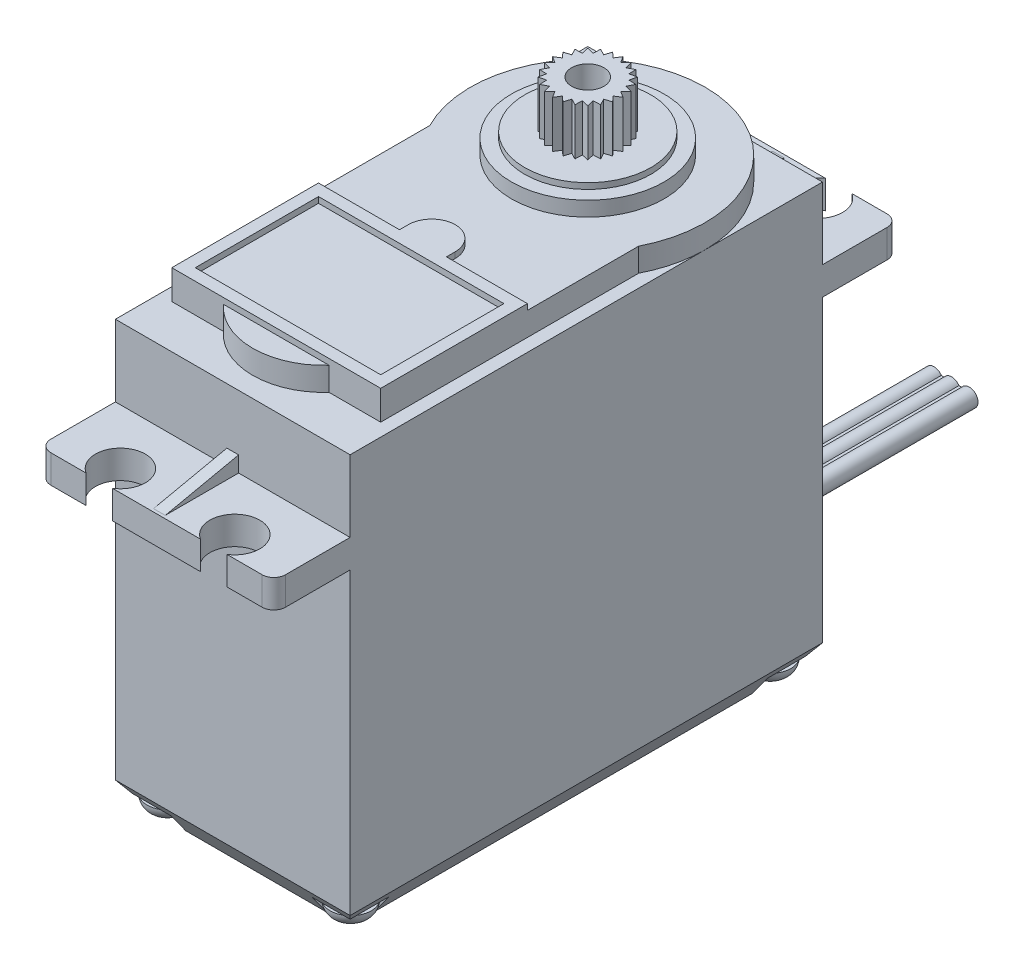
SolidWorks part; units mm, degrees
ref_plane "Front" through (0, 0, 0) normal (0, 0, 1) x (1, 0, 0)
ref_plane "Top" through (0, 0, 0) normal (0, 1, 0) x (1, 0, 0)
ref_plane "Right" through (0, 0, 0) normal (1, 0, 0) x (0, 0, -1)
sketch "Sketch1" plane through (0, 0, 0) normal (0, 1, 0) x (1, 0, 0)
  line L5 (-10, 20.125) -> (10, 20.125)
  line L6 (-10, 20.125) -> (-10, -20.125)
  line L7 (-10, -20.125) -> (10, -20.125)
  line L8 (10, 20.125) -> (10, -20.125)
  line L9 (-10, 20.125) -> (10, -20.125) construction
  line L10 (-10, -20.125) -> (10, 20.125) construction
  point P0 (0, 0)
  dimension "D1" = 20
  dimension "D2" = 40.25
extrude "Boss-Extrude1" add sketch "Sketch1" along normal mid plane 36.75
ref_plane "Plane1" through (0, 9.875, 0) normal (0, 1, 0) x (1, 0, 0)
sketch "Sketch2" plane through (0, 9.875, 0) normal (0, 1, 0) x (1, 0, 0)
  line L0 (-10, -20.125) -> (-10, -26.625)
  line L1 (-10, -26.625) -> (-6, -26.625)
  line L2 (-3.75, -26.625) -> (3.75, -26.625)
  line L3 (6, -26.625) -> (10, -26.625)
  line L4 (10, -26.625) -> (10, -20.125)
  line L5 (0, -26.625) -> (0, -20.125) construction
  line L6 (-10, -20.125) -> (10, -20.125) construction
  line L7 (-10, -20.125) -> (10, -20.125)
  arc A0 (-6, -26.625) -> (-3.75, -26.625) centre (-4.875, -24.8222) cw
  arc A1 (3.75, -26.625) -> (6, -26.625) centre (4.875, -24.8222) cw
  dimension "D1" = 2.125
  dimension "D2" = 7.5
  dimension "D3" = 6.5
  dimension "D4" = 2.25
extrude "Boss-Extrude2" add sketch "Sketch2" along normal blind 2.4
sketch "Sketch3" plane through (0, 0, 0) normal (1, 0, 0) x (0, 0, -1)
  line L0 (-20.125, 13.615) -> (-26.375, 12.275)
  line L1 (-20.125, 18.375) -> (-20.125, 12.275) construction
  line L2 (-26.375, 12.275) -> (-20.125, 12.275)
  line L3 (-20.125, 12.275) -> (-26.625, 12.275) construction
  line L4 (-20.125, 12.275) -> (-20.125, 13.615)
  line L5 (-26.625, 12.275) -> (-26.625, 9.875) construction
  dimension "D1" = 1.34
  dimension "D2" = 0.25
extrude "Boss-Extrude3" add sketch "Sketch3" along normal mid plane 1
sketch "Sketch4" plane through (0, 18.375, 0) normal (0, 1, 0) x (1, 0, 0)
  line L0 (-10, 20.125) -> (-10, -20.125) construction
  line L1 (10, -20.125) -> (10, 20.125) construction
  line L2 (-8.9, 5.5654) -> (-8.9, -16.419)
  line L3 (-8.9, -16.419) -> (-4.5, -16.419)
  line L4 (4.5, -16.419) -> (8.9, -16.419)
  line L5 (8.9, -16.419) -> (8.9, 5.5654)
  line L6 (-4.5, -16.419) -> (4.5, -16.419) construction
  line L7 (0, -16.419) -> (0, -18.419) construction
  line L12 (10, -20.125) -> (10, 20.125)
  line L13 (10, 20.125) -> (-10, 20.125)
  line L14 (-10, 20.125) -> (-10, -20.125)
  line L15 (-10, -20.125) -> (10, -20.125)
  line L16 (10, -20.125) -> (10, 20.125)
  line L17 (10, 20.125) -> (-10, 20.125)
  line L18 (-10, 20.125) -> (-10, -20.125)
  line L19 (-10, -20.125) -> (10, -20.125)
  arc A0 (-8.9, 5.5654) -> (8.9, 5.5654) centre (0, 10.125) cw
  arc A2 (-4.5, -16.419) -> (4.5, -16.419) centre (0, -12.3565) ccw
  dimension "D1" = 17.8
  dimension "D2" = 9
  dimension "D4" = 2
  dimension "D3" = 0
extrude "Boss-Extrude4" add sketch "Sketch4" along normal blind 2 contours L3 A2 L4 L5 A0 L2 region at (0, 18.375, -0.9438)
sketch "Sketch5" plane through (0, 20.375, 0) normal (0, 1, 0) x (1, 0, 0)
  circle A0 centre (0, 10.125) radius 6.5
  dimension "D1" = 13
extrude "Boss-Extrude5" add sketch "Sketch5" along normal blind 1.75
sketch "Sketch6" plane through (0, 22.125, 0) normal (0, 1, 0) x (1, 0, 0)
  circle A0 centre (0, 10.125) radius 6.5
  circle A1 centre (0, 10.125) radius 5.375
  circle A2 centre (0, 10.125) radius 6.5 construction
  dimension "D1" = 10.75
extrude "Cut-Extrude1" cut sketch "Sketch6" against normal blind 0.5
sketch "Sketch7" plane through (0, 22.125, 0) normal (0, 1, 0) x (1, 0, 0)
  line L0 (-0.3263, 12.6036) -> (0, 13.125)
  line L1 (0, 13.125) -> (0.3263, 12.6036)
  line L2 (-0.3263, 12.6036) -> (0.3263, 12.6036) construction
  line L3 (0, 12.6036) -> (0, 10.125) construction
  line L4 (-0.3263, 12.6036) -> (0, 10.125) construction
  line L5 (0, 10.125) -> (0.3263, 12.6036) construction
  line L6 (0.7765, 13.0228) -> (0.9567, 12.4347)
  line L7 (0.3263, 12.6036) -> (0.7765, 13.0228)
  line L8 (1.5, 12.7231) -> (1.5219, 12.1084)
  line L9 (0.9567, 12.4347) -> (1.5, 12.7231)
  line L10 (2.1213, 12.2463) -> (1.9834, 11.6469)
  line L11 (1.5219, 12.1084) -> (2.1213, 12.2463)
  line L12 (2.5981, 11.625) -> (2.3097, 11.0817)
  line L13 (1.9834, 11.6469) -> (2.5981, 11.625)
  line L14 (2.8978, 10.9015) -> (2.4786, 10.4513)
  line L15 (2.3097, 11.0817) -> (2.8978, 10.9015)
  line L16 (3, 10.125) -> (2.4786, 9.7987)
  line L17 (2.4786, 10.4513) -> (3, 10.125)
  line L18 (2.8978, 9.3485) -> (2.3097, 9.1683)
  line L19 (2.4786, 9.7987) -> (2.8978, 9.3485)
  line L20 (2.5981, 8.625) -> (1.9834, 8.6031)
  line L21 (2.3097, 9.1683) -> (2.5981, 8.625)
  line L22 (2.1213, 8.0037) -> (1.5219, 8.1416)
  line L23 (1.9834, 8.6031) -> (2.1213, 8.0037)
  line L24 (1.5, 7.5269) -> (0.9567, 7.8153)
  line L25 (1.5219, 8.1416) -> (1.5, 7.5269)
  line L26 (0.7765, 7.2272) -> (0.3263, 7.6464)
  line L27 (0.9567, 7.8153) -> (0.7765, 7.2272)
  line L28 (0, 7.125) -> (-0.3263, 7.6464)
  line L29 (0.3263, 7.6464) -> (0, 7.125)
  line L30 (-0.7765, 7.2272) -> (-0.9567, 7.8153)
  line L31 (-0.3263, 7.6464) -> (-0.7765, 7.2272)
  line L32 (-1.5, 7.5269) -> (-1.5219, 8.1416)
  line L33 (-0.9567, 7.8153) -> (-1.5, 7.5269)
  line L34 (-2.1213, 8.0037) -> (-1.9834, 8.6031)
  line L35 (-1.5219, 8.1416) -> (-2.1213, 8.0037)
  line L36 (-2.5981, 8.625) -> (-2.3097, 9.1683)
  line L37 (-1.9834, 8.6031) -> (-2.5981, 8.625)
  line L38 (-2.8978, 9.3485) -> (-2.4786, 9.7987)
  line L39 (-2.3097, 9.1683) -> (-2.8978, 9.3485)
  line L40 (-3, 10.125) -> (-2.4786, 10.4513)
  line L41 (-2.4786, 9.7987) -> (-3, 10.125)
  line L42 (-2.8978, 10.9015) -> (-2.3097, 11.0817)
  line L43 (-2.4786, 10.4513) -> (-2.8978, 10.9015)
  line L44 (-2.5981, 11.625) -> (-1.9834, 11.6469)
  line L45 (-2.3097, 11.0817) -> (-2.5981, 11.625)
  line L46 (-2.1213, 12.2463) -> (-1.5219, 12.1084)
  line L47 (-1.9834, 11.6469) -> (-2.1213, 12.2463)
  line L48 (-1.5, 12.7231) -> (-0.9567, 12.4347)
  line L49 (-1.5219, 12.1084) -> (-1.5, 12.7231)
  line L50 (-0.7765, 13.0228) -> (-0.3263, 12.6036)
  line L51 (-0.9567, 12.4347) -> (-0.7765, 13.0228)
  circle A0 centre (0, 10.125) radius 2.5 construction
  point P79 (0, 10.125)
  dimension "D4" = 5
  dimension "D1" = 3
  dimension "D3" = 24
extrude "Boss-Extrude6" add sketch "Sketch7" along normal blind 4 contours L51 L48 L49 L46 L47 L44 L45 L42 L43 L40 L41 L38 L39 L36 L37 L34 L35 L32 L33 L30 L31 L28 L29 L26 L27 L24 L25 L22 L23 L20 L21 L18 L19 L16 L17 L14 L15 L12 L13 L10 L11 L8 L9 L6 L7 L1 L0 L50 region at (0, 22.125, -10.125)
sketch "Sketch8" plane through (0, 26.125, 0) normal (0, 1, 0) x (1, 0, 0)
  circle A0 centre (0, 10.125) radius 1.375
  circle A2 centre (0, 10.125) radius 5.375 construction
  dimension "D1" = 2.75
extrude "Cut-Extrude2" cut sketch "Sketch8" against normal blind 6
sketch "Sketch9" plane through (0, 20.375, 0) normal (0, 1, 0) x (1, 0, 0)
  line L0 (8.9, -16.419) -> (-8.9, -16.419)
  line L1 (-8.9, -16.419) -> (-8.9, -3.919)
  line L2 (-8.9, 5.5654) -> (-8.9, -16.419) construction
  line L3 (-8.9, -3.919) -> (-2, -3.919)
  line L4 (8.9, -16.419) -> (8.9, 5.5654) construction
  line L5 (8.9, -3.919) -> (8.9, -16.419)
  line L6 (2, -3.919) -> (2, -3.169)
  line L7 (-2, -3.169) -> (-2, -3.919)
  line L8 (2, -3.919) -> (8.9, -3.919)
  line L9 (2, -4.919) -> (7.9, -4.919)
  line L10 (7.9, -4.919) -> (7.9, -15.419)
  line L11 (7.9, -15.419) -> (-7.9, -15.419)
  line L12 (-7.9, -15.419) -> (-7.9, -4.919)
  line L13 (-7.9, -4.919) -> (-2, -4.919)
  line L14 (2, -4.919) -> (-2, -4.919)
  arc A0 (2, -3.169) -> (-2, -3.169) centre (0, -3.169) ccw
  point P16 (0, -1.169)
  dimension "D2" = 2
  dimension "D1" = 12.5
  dimension "D3" = 2.75
  dimension "D4" = 1
extrude "Boss-Extrude7" add sketch "Sketch9" along normal blind 0.5
fillet "Fillet1" radius 1 2 edges at (10, 11.075, 26.625) (-10, 11.075, 26.625)
mirror "Mirror1" about plane through (0, 0, 0) normal (0, 0, 1) of "Fillet1", "Boss-Extrude2", "Boss-Extrude3"
chamfer "Chamfer1" distance 2 distance2 2.75 4 edges at (0, -18.375, 20.125) (-10, -18.375, 0) (0, -18.375, -20.125) (10, -18.375, 0) first distance on face at (0, -18.375, 0)
sketch "Sketch10" plane through (0, -18.375, 0) normal (0, -1, 0) x (1, 0, 0)
  line L0 (6, -20.125) -> (6, -18.125)
  line L1 (10, -20.125) -> (-10, -20.125) construction
  line L3 (8, -16.125) -> (10, -16.125)
  line L4 (10, 20.125) -> (10, -20.125) construction
  line L5 (10, -16.125) -> (10, -20.125)
  line L6 (10, -20.125) -> (6, -20.125)
  line L7 (-8, -18.125) -> (8, -18.125) construction
  arc A0 (6, -18.125) -> (8, -16.125) centre (8, -18.125) cw
  dimension "D1" = 4
  dimension "D2" = 4
extrude "Cut-Extrude3" cut sketch "Sketch10" against normal blind 1.75
ref_plane "Plane2" through (0, 0, -17.875) normal (0, 0, -1) x (-1, 0, 0)
sketch "Sketch12" plane through (0, 0, -17.875) normal (0, 0, -1) x (-1, 0, 0)
  line L0 (-7.8, -16.625) -> (-9.55, -16.625)
  line L2 (-8, -16.625) -> (-6, -16.625) construction
  line L4 (-7.8, -17.75) -> (-7.8, -16.625)
  line L5 (-7.8, -17.75) -> (-8.425, -17.75)
  line L6 (-10, 9.875) -> (-10, -15.625) construction
  arc A0 (-9.55, -16.625) -> (-8.425, -17.75) centre (-8.425, -16.625) ccw
  dimension "D1" = 2.2
  dimension "D2" = 1.125
  dimension "D3" = 1.75
revolve "Revolve1" add sketch "Sketch12" angle 360 about L4
mirror "Mirror2" about plane through (0, 0, 0) normal (1, 0, 0) of "Cut-Extrude3", "Revolve1"
mirror "Mirror3" about plane through (0, 0, 0) normal (0, 0, 1) of "Mirror2"
sketch "Sketch13" plane through (0, 0, -20.125) normal (0, 0, -1) x (-1, 0, 0)
  line L0 (0, -10.125) -> (0, 0) construction
  line L1 (-3.25, -14.375) -> (3.25, -14.375)
  line L2 (-3.25, -14.375) -> (-3.25, -10.125)
  line L3 (-3.25, -10.125) -> (3.25, -10.125)
  line L4 (3.25, -14.375) -> (3.25, -10.125)
  line L6 (6, -18.375) -> (-6, -18.375) construction
  dimension "D1" = 6.5
  dimension "D2" = 4.25
  dimension "D3" = 4
extrude "Boss-Extrude8" add sketch "Sketch13" along normal blind 1
sketch "Sketch15" plane through (0, 0, -21.125) normal (0, 0, -1) x (-1, 0, 0)
  line L8 (-2.75, -10.625) -> (-2.75, -13.875)
  line L9 (-2.75, -13.875) -> (2.75, -13.875)
  line L10 (2.75, -13.875) -> (2.75, -10.625)
  line L11 (2.75, -10.625) -> (-2.75, -10.625)
  line L12 (-2.75, -10.625) -> (-2.75, -13.875)
  line L13 (-2.75, -13.875) -> (2.75, -13.875)
  line L14 (2.75, -13.875) -> (2.75, -10.625)
  line L15 (2.75, -10.625) -> (-2.75, -10.625)
  dimension "D1" = 0.5
sketch "Sketch18" plane through (0, 0, -21.125) normal (0, 0, -1) x (-1, 0, 0)
  line L0 (0, -12.25) -> (0, -10.125) construction
  line L1 (0, -12.25) -> (0, -14.375) construction
  line L2 (3.25, -10.125) -> (-3.25, -10.125) construction
  line L3 (-3.25, -14.375) -> (3.25, -14.375) construction
  line L4 (-0.875, -12.6646) -> (-0.625, -12.6646)
  line L5 (0.625, -12.6646) -> (0.875, -12.6646)
  line L6 (0.875, -11.8354) -> (0.625, -11.8354)
  line L7 (-0.875, -11.8354) -> (-0.625, -11.8354)
  arc A0 (-0.875, -11.8354) -> (-0.875, -12.6646) centre (-1.5, -12.25) ccw
  arc A1 (-0.625, -12.6646) -> (0.625, -12.6646) centre (0, -12.25) ccw
  arc A2 (0.875, -12.6646) -> (0.875, -11.8354) centre (1.5, -12.25) ccw
  arc A3 (0.625, -11.8354) -> (-0.625, -11.8354) centre (0, -12.25) ccw
  dimension "D1" = 1.5
  dimension "D2" = 0.25
extrude "Boss-Extrude10" add sketch "Sketch18" along normal blind 20
ref_plane "Plane3" through (0, 0, -25.125) normal (0, 0, -1) x (-1, 0, 0)
sketch "Sketch16" plane through (0, 0, -25.125) normal (0, 0, -1) x (-1, 0, 0)
  line L0 (-2.75, -10.625) -> (2.75, -13.875) construction
  line L1 (-2.75, -13.875) -> (2.75, -10.625) construction
  line L2 (-2.375, -12.25) -> (-2.25, -12.25) construction
  line L3 (-2.375, -13.125) -> (2.375, -13.125)
  line L4 (-2.375, -13.125) -> (-2.375, -11.375)
  line L5 (-2.375, -11.375) -> (2.375, -11.375)
  line L6 (2.375, -13.125) -> (2.375, -11.375)
  line L7 (-2.375, -13.125) -> (2.375, -11.375) construction
  line L8 (-2.375, -11.375) -> (2.375, -13.125) construction
  line L9 (0, -13) -> (0, -13.125) construction
  arc A1 (-0.875, -11.8354) -> (-0.875, -12.6646) centre (-1.5, -12.25) ccw construction
  arc A2 (-0.625, -12.6646) -> (0.625, -12.6646) centre (0, -12.25) ccw construction
  point P8 (0, -12.25)
  point P10 (0, -12.25)
  dimension "D1" = 0.125
  dimension "D2" = 0.125
loft "Loft1" add profiles "Sketch16", "Sketch15" connector at (2.375, -13.125, -25.125) connector at (2.75, -13.875, -21.125)
ref_axis "Axis1" through (0, 20.125, -10.125) along (0, 1, 0)
